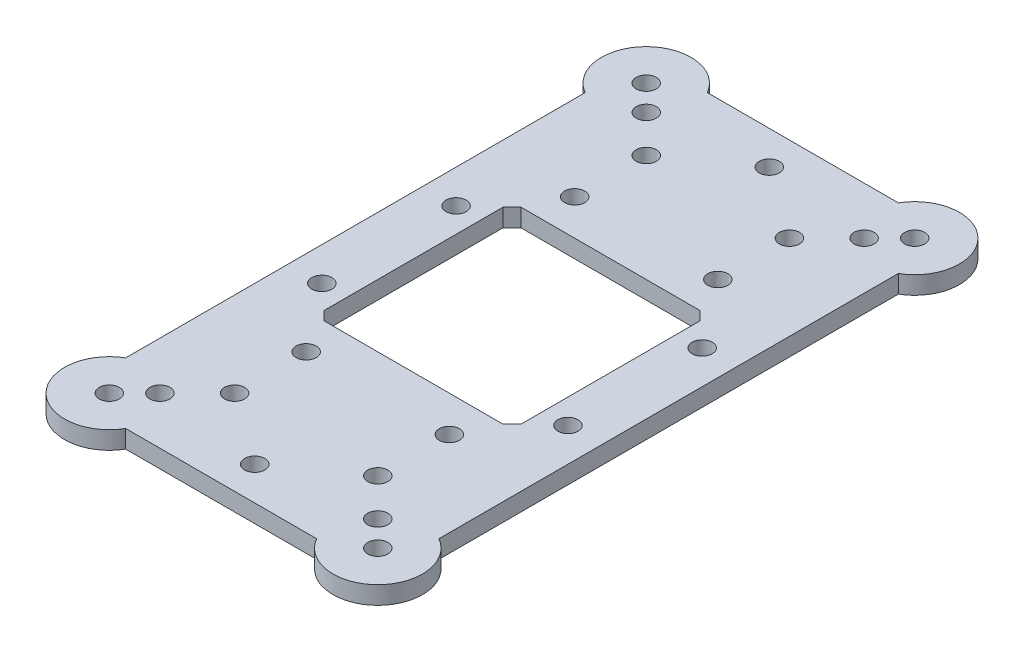
SolidWorks part; units mm, degrees
material "1060 Alloy"
ref_plane "Front Plane" through (0, 0, 0) normal (0, 0, 1) x (1, 0, 0)
ref_plane "Top Plane" through (0, 0, 0) normal (0, 1, 0) x (1, 0, 0)
ref_plane "Right Plane" through (0, 0, 0) normal (1, 0, 0) x (0, 0, -1)
sketch "Sketch1" plane through (0, 0, 0) normal (0, 1, 0) x (1, 0, 0)
  line L0 (30, -60) -> (-30, 60) construction
  line L1 (-30, 60) -> (30, 60) construction
  line L2 (-30, 60) -> (-30, -60) construction
  line L3 (-30, -60) -> (30, -60) construction
  line L4 (30, 60) -> (30, -60) construction
  line L5 (-30, 0) -> (-30, 42.6795)
  line L6 (-12.6795, 60) -> (0, 60)
  line L7 (30, 42.6795) -> (30, 0)
  line L8 (0, 60) -> (12.6795, 60)
  line L9 (12.6795, -60) -> (0, -60)
  line L10 (30, 0) -> (30, -42.6795)
  line L11 (-30, -42.6795) -> (-30, 0)
  line L12 (0, -60) -> (-12.6795, -60)
  line L13 (-30, 0) -> (30, 0) construction
  line L14 (0, 60) -> (0, -60) construction
  circle A0 centre (-30, 60) radius 2.25
  circle A1 centre (30, 60) radius 2.25
  circle A2 centre (30, -60) radius 2.25
  circle A3 centre (-30, -60) radius 2.25
  arc A4 (-35, 51.3397) -> (-21.3397, 65) centre (-30, 60) cw
  arc A5 (21.3397, 65) -> (35, 51.3397) centre (30, 60) cw
  arc A6 (35, -51.3397) -> (21.3397, -65) centre (30, -60) cw
  arc A7 (-21.3397, -65) -> (-35, -51.3397) centre (-30, -60) cw
  arc A8 (-30, -42.6795) -> (-35, -51.3397) centre (-40, -42.6795) cw
  arc A9 (-21.3397, -65) -> (-12.6795, -60) centre (-12.6795, -70) cw
  arc A10 (35, -51.3397) -> (30, -42.6795) centre (40, -42.6795) cw
  arc A11 (30, 42.6795) -> (35, 51.3397) centre (40, 42.6795) cw
  arc A12 (21.3397, 65) -> (12.6795, 60) centre (12.6795, 70) cw
  arc A13 (-21.3397, 65) -> (-12.6795, 60) centre (-12.6795, 70) ccw
  arc A14 (-30, 42.6795) -> (-35, 51.3397) centre (-40, 42.6795) ccw
  arc A15 (12.6795, -60) -> (21.3397, -65) centre (12.6795, -70) cw
  point P32 (0, 0)
  point P38 (-20, 60)
  point P41 (-30, 50)
  dimension "D2" = 4.5
  dimension "D3" = 10
  dimension "D5" = 10
  dimension "D6" = 10
  dimension "D1" = 60
  dimension "D4" = 120
sheet metal parameters "Sheet-Metal1" thickness 4 parameters "D1"=5
base flange "Base-Flange1" sketch "Sketch1" thickness 4 reverse thickness direction no parameters "D1"=5
sketch "Sketch4" plane through (0, 0, 0) normal (0, 1, 0) x (1, 0, 0)
  line L1 (-20, 22) -> (20, 22)
  line L2 (-22, 20) -> (-22, -20)
  line L3 (-20, -22) -> (20, -22)
  line L4 (22, 20) -> (22, -20)
  line L5 (22, 22) -> (-22, -22) construction
  line L6 (-22, 20) -> (-20, 22)
  line L7 (-22, -20) -> (-20, -22)
  line L8 (20, -22) -> (22, -20)
  line L9 (20, 22) -> (22, 20)
  point P0 (-22, 22)
  point P1 (22, -22)
  dimension "D1" = 44
  dimension "D2" = 44
extrude "Cut-Extrude1" cut sketch "Sketch4" against normal up to next normal cut yes
sketch "Sketch5" plane through (0, -4, 0) normal (0, -1, 0) x (1, 0, 0)
  line L0 (-30, 60) -> (-24.3431, 54.3431) construction
  line L1 (-24.3431, 54.3431) -> (0, 30) construction
  line L2 (30, 60) -> (24.3431, 54.3431) construction
  line L3 (-24.3431, -54.3431) -> (0, -30) construction
  line L4 (30, -60) -> (24.3431, -54.3431) construction
  line L5 (0, -30) -> (24.3431, -54.3431) construction
  line L6 (-30, -60) -> (-24.3431, -54.3431) construction
  line L7 (0, 30) -> (24.3431, 54.3431) construction
  circle A0 centre (-24.3431, 54.3431) radius 2.25
  circle A1 centre (24.3431, 54.3431) radius 2.25
  circle A2 centre (24.3431, -54.3431) radius 2.25
  circle A3 centre (-24.3431, -54.3431) radius 2.25
  point P18 (0, 0)
  dimension "D1" = 4.5
  dimension "D2" = 8
extrude "Cut-Extrude2" cut sketch "Sketch5" against normal through all normal cut yes
sketch "Sketch6" plane through (0, -4, 0) normal (0, -1, 0) x (1, 0, 0)
  line L0 (27.5, -15) -> (-27.5, -15) construction
  line L1 (-27.5, -15) -> (-27.5, 15) construction
  line L2 (-27.5, 15) -> (27.5, 15) construction
  line L3 (27.5, 15) -> (27.5, -15) construction
  line L4 (27.5, -15) -> (-27.5, 15) construction
  circle A0 centre (-27.5, -15) radius 2.25
  circle A1 centre (-27.5, 15) radius 2.25
  circle A2 centre (27.5, 15) radius 2.25
  circle A3 centre (27.5, -15) radius 2.25
  dimension "D3" = 4.5
  dimension "D1" = 55
  dimension "D2" = 30
extrude "Cut-Extrude3" cut sketch "Sketch6" against normal through all normal cut yes
sketch "Sketch7" plane through (0, 0, 0) normal (0, 1, 0) x (1, 0, 0)
  line L0 (-30, 42.6795) -> (-30, -42.6795) construction
  line L1 (-35, 51.3397) -> (-30, 51.3397)
  line L2 (-35, 51.3397) -> (-35, -51.3397)
  line L3 (-35, -51.3397) -> (-30, -51.3397)
  line L4 (-30, 51.3397) -> (-30, -51.3397)
  line L5 (30, -42.6795) -> (30, 42.6795) construction
  line L6 (35, 51.3397) -> (30, 51.3397)
  line L7 (35, 51.3397) -> (35, -51.3397)
  line L8 (35, -51.3397) -> (30, -51.3397)
  line L9 (30, 51.3397) -> (30, -51.3397)
  line L10 (-12.6795, -60) -> (12.6795, -60) construction
  line L11 (-21.3397, -65) -> (21.3397, -65)
  line L12 (-21.3397, -65) -> (-21.3397, -60)
  line L13 (-21.3397, -60) -> (21.3397, -60)
  line L14 (21.3397, -65) -> (21.3397, -60)
  line L15 (-21.3397, 65) -> (21.3397, 65)
  line L16 (-21.3397, 65) -> (-21.3397, 60)
  line L17 (-21.3397, 60) -> (21.3397, 60)
  line L18 (21.3397, 65) -> (21.3397, 60)
  line L19 (12.6795, 60) -> (-12.6795, 60) construction
base flange "Tab1" sketch "Sketch7" thickness 4 reverse thickness direction no parameters "D1"=5
sketch "Sketch8" plane through (0, -4, 0) normal (0, -1, 0) x (1, 0, 0)
  line L0 (-16, 46) -> (-16, 30) construction
  line L1 (-16, 30) -> (16, 30) construction
  line L2 (16, 30) -> (16, 46) construction
  line L3 (16, 46) -> (-16, 46) construction
  line L4 (-16, 38) -> (16, 38) construction
  line L5 (0, 38) -> (0, -38) construction
  line L7 (0, 0) -> (11.0496, 0) construction
  line L8 (-16, -38) -> (16, -38) construction
  line L9 (16, -46) -> (-16, -46) construction
  line L10 (16, -30) -> (16, -46) construction
  line L11 (-16, -30) -> (16, -30) construction
  line L12 (-16, -46) -> (-16, -30) construction
  circle A0 centre (-16, 46) radius 2.25
  circle A1 centre (-16, 30) radius 2.25
  circle A2 centre (16, 46) radius 2.25
  circle A3 centre (16, 30) radius 2.25
  circle A4 centre (16, -30) radius 2.25
  circle A5 centre (16, -46) radius 2.25
  circle A6 centre (-16, -30) radius 2.25
  circle A7 centre (-16, -46) radius 2.25
  dimension "D1" = 4.5
  dimension "D2" = 32
  dimension "D3" = 16
  dimension "D4" = 38
extrude "Cut-Extrude4" cut sketch "Sketch8" against normal through all normal cut yes
sketch "Sketch9" plane through (0, 0, 0) normal (0, 1, 0) x (1, 0, 0)
  line L0 (0, 60) -> (0, -60) construction
  line L1 (0, -57.5) -> (0, 57.5) construction
  line L2 (-25, 0) -> (25, 0) construction
  circle A0 centre (0, 57.5) radius 2.25
  circle A1 centre (-25, 0) radius 2.25 construction
  circle A2 centre (25, 0) radius 2.25 construction
  circle A3 centre (0, -57.5) radius 2.25
  dimension "D3" = 4.5
  dimension "D1" = 115
  dimension "D2" = 50
extrude "Cut-Extrude5" cut sketch "Sketch9" against normal through all normal cut yes
flat pattern "Flat-Pattern1" [suppressed]
sketch "Bend-Lines1" plane through (0, 0, 0) normal (0, 1, 0) x (1, 0, 0)
sketch3d "Bounding-Box1" [suppressed]
  line L0 (0, 27.3205, 0) -> (0, -112.6795, 0) construction
  line L1 (80, 27.3205, 0) -> (80, -112.6795, 0) construction
  line L2 (0, 27.3205, 0) -> (80, 27.3205, 0) construction
  line L3 (0, -112.6795, 0) -> (80, -112.6795, 0) construction
